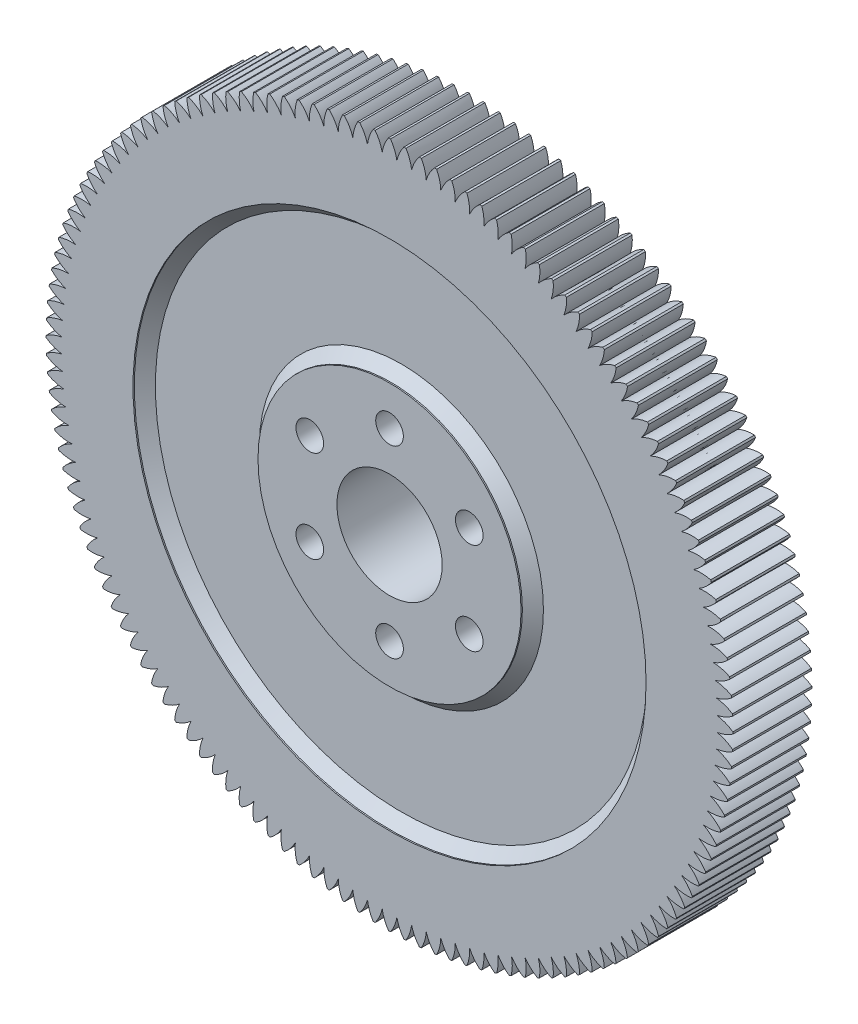
SolidWorks part; units mm, degrees
material "Cast iron, gray, flake graphite, EN GJL 250"
ref_plane "Front Plane" through (0, 0, 0) normal (0, 0, 1) x (1, 0, 0)
ref_plane "Top Plane" through (0, 0, 0) normal (0, 1, 0) x (1, 0, 0)
ref_plane "Right Plane" through (0, 0, 0) normal (1, 0, 0) x (0, 0, -1)
sketch "Sketch8" plane through (0, 0, 0) normal (0, 0, 1) x (1, 0, 0)
  circle A0 centre (0, 0) radius 97.5
  circle A1 centre (0, 0) radius 122.5
  dimension "D1" = 245
  dimension "D2" = 195
extrude "Boss-Extrude1" add sketch "Sketch8" along normal mid plane 30
sketch "Sketch9" plane through (0, 0, 0) normal (0, 0, 1) x (1, 0, 0)
  circle A0 centre (0, 0) radius 50
  dimension "D1" = 100
extrude "Boss-Extrude2" add sketch "Sketch9" along normal mid plane 30 separate body
sketch "Sketch10" plane through (0, 0, 0) normal (0, 0, 1) x (1, 0, 0)
  circle A0 centre (0, 0) radius 50
  circle A1 centre (0, 0) radius 97.5
  circle A2 centre (0, 0) radius 50 construction
  circle A3 centre (0, 0) radius 97.5 construction
extrude "Boss-Extrude3" add sketch "Sketch10" along normal mid plane 21
chamfer "Chamfer2" distance 4 angle 45 4 edges at (97.5, 0, 10.5) (50, 0, 10.5) (97.5, 0, -10.5) (50, 0, -10.5)
sketch "Sketch11" plane through (0, 0, 15) normal (0, 0, 1) x (1, 0, 0)
  circle A0 centre (0, 0) radius 20
  dimension "D1" = 40
extrude "Cut-Extrude1" cut sketch "Sketch11" against normal through all
ref_axis "Axis1" through (0, 0, -2.82) along (0, 0, 1)
sketch "Sketch13" plane through (0, 0, 15) normal (0, 0, 1) x (1, 0, 0)
  line L0 (-0.375, 130.5) -> (0.375, 130.5)
  line L1 (4.7384, 137.8027) -> (-5.4884, 123.1973) construction
  line L2 (0, 130.5) -> (0, 122.5) construction
  circle A0 centre (0, 0) radius 122.5 construction
  arc A1 (3, 122.4633) -> (-3, 122.4633) centre (0, 0) ccw
  spline S0 degree 2 poles (-3, 122.4633) (-2.8086, 127.0245) (-0.375, 130.5) knots 0 0 0 0.951846 0.951846 0.951846
  spline S1 degree 2 poles (3, 122.4633) (2.8086, 127.0245) (0.375, 130.5) knots 0 0 0 0.951846 0.951846 0.951846
  dimension "D1" = 55
  dimension "D3" = 8
  dimension "D4" = 6
  dimension "D5" = 8.4857
  dimension "D2" = 0.75
extrude "Boss-Extrude4" add sketch "Sketch13" against normal up to surface (30 mm away) up to face at (122.5, 0, -15)
pattern_circular "CirPattern2" count 140 over 360 about axis through (0, 0, 15) along (0, 0, -1) of "Boss-Extrude4"
hole_wizard "M12x1.5 Tapped Hole1" positions "Sketch14" profile "Sketch15" tap size "M12x1.5" standard "ANSI Metric" end condition through all
sketch "Sketch14" plane through (0, 0, 15) normal (0, 0, 1) x (1, 0, 0)
  line L1 (0, 20) -> (0, 50) construction
  circle A4 centre (0, 0) radius 50 construction
  circle A5 centre (0, 0) radius 20 construction
  point P127 (0, 35)
cosmetic thread "Hole Thread1" parameters "D2"=12
sketch "Sketch15" plane through (0, 35, 15) normal (1, 0, 0) x (0, -1, 0)
  line L0 (0, 0) -> (0, 30)
  line L1 (0, 30) -> (5.25, 30)
  line L2 (5.25, 30) -> (5.25, 0)
  line L5 (5.25, 0) -> (0, 0)
  line L11 (0, -6.35) -> (0, 107.95) construction
  dimension "Thru Tap Drill Dia." = 10.5
  dimension "Thru Tap Drill Depth" = 30
pattern_circular "CirPattern3" count 6 over 360 about axis through (0, 0, -2.82) along (0, 0, 1) of "M12x1.5 Tapped Hole1"
cosmetic thread "Hole Thread2" parameters "D2"=12
cosmetic thread "Hole Thread3" parameters "D2"=12
cosmetic thread "Hole Thread4" parameters "D2"=12
cosmetic thread "Hole Thread5" parameters "D2"=12
cosmetic thread "Hole Thread6" parameters "D2"=12
equation "\"Flywheel Diameter\"= 245mm"
equation "\"Crankshaft Radius\"= 40mm"
equation "\"Flywheel Thickness\" = 30mm"
equation "\"D1@Sketch8\"=\"Flywheel Diameter\""
equation "\"D2@Sketch8\"=\"Flywheel Diameter\"-50mm"
equation "\"D1@Boss-Extrude1\"=\"Flywheel Thickness\""
equation "\"Hub Diameter\"= \"Crankshaft Radius\" + 60mm"
equation "\"D1@Sketch9\"=\"Hub Diameter\""
equation "\"D1@Boss-Extrude2\"=\"Flywheel Thickness\""
equation "\"D1@Boss-Extrude3\"=\"Flywheel Thickness\"*0.7"
equation "\"D1@Sketch11\"=\"Crankshaft Radius\""
